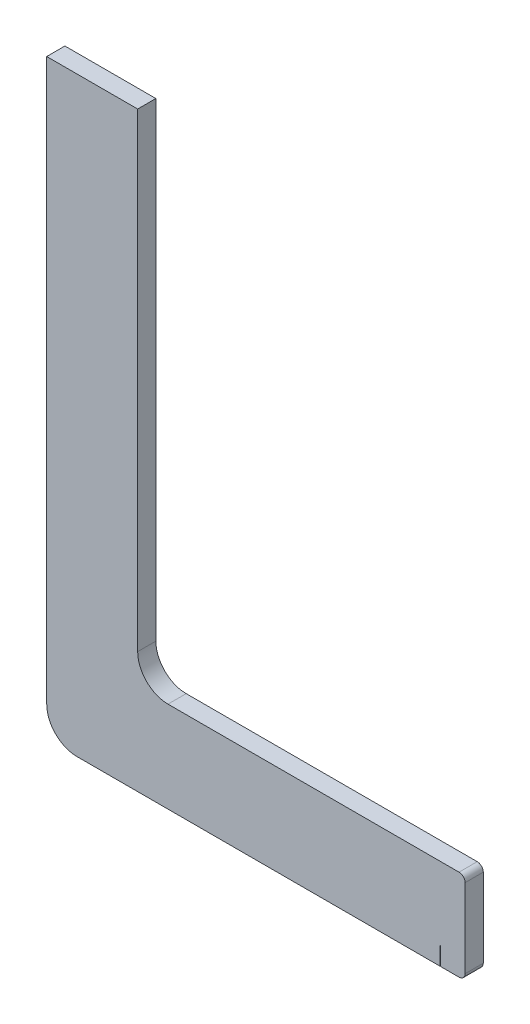
SolidWorks part; units mm, degrees
ref_plane "Front Plane" through (0, 0, 0) normal (0, 0, 1) x (1, 0, 0)
ref_plane "Top Plane" through (0, 0, 0) normal (0, 1, 0) x (1, 0, 0)
ref_plane "Right Plane" through (0, 0, 0) normal (1, 0, 0) x (0, 0, -1)
sketch "Sketch1" plane through (0, 0, 0) normal (0, 0, 1) x (1, 0, 0)
  line L0 (0, -1) -> (0, -92.5)
  line L1 (5, -97.5) -> (68, -97.5)
  line L2 (69, -96.5) -> (69, -83.5)
  line L3 (68, -82.5) -> (20, -82.5)
  line L4 (15, -77.5) -> (15, -1)
  line L5 (14, 0) -> (1, 0)
  line L6 (15, -1) -> (15, 0)
  line L7 (15, 0) -> (14, 0)
  line L8 (0, -1) -> (0, 0)
  line L9 (0, 0) -> (1, 0)
  arc A2 (69, -96.5) -> (68, -97.5) centre (68, -96.5) cw
  arc A3 (69, -83.5) -> (68, -82.5) centre (68, -83.5) ccw
  arc A4 (5, -97.5) -> (0, -92.5) centre (5, -92.5) cw
  arc A5 (15, -77.5) -> (20, -82.5) centre (20, -77.5) ccw
  point P9 (0, 0)
  point P12 (15, 0)
  point P15 (69, -97.5)
  point P18 (69, -82.5)
  point P21 (0, -97.5)
  point P24 (15, -82.5)
  dimension "D6" = 5
  dimension "D1" = 82.5
  dimension "D2" = 15
  dimension "D3" = 69
  dimension "D4" = 15
extrude "Boss-Extrude1" add sketch "Sketch1" along normal blind 3
sketch "Sketch2" plane through (0, -97.5, 0) normal (0, -1, 0) x (1, 0, 0)
  line L0 (0, 1.5) -> (64.9, 1.5) construction
  line L1 (0, 3) -> (0, 0) construction
  line L2 (5, 3) -> (68, 3) construction
  line L3 (64.85, 0) -> (64.95, 0)
  line L4 (64.85, 0) -> (64.85, 3)
  line L5 (64.85, 3) -> (64.95, 3)
  line L6 (64.95, 0) -> (64.95, 3)
  line L7 (64.85, 0) -> (64.95, 3) construction
  line L8 (64.85, 3) -> (64.95, 0) construction
  dimension "D1" = 64.9
  dimension "D2" = 0.1
extrude "Cut-Extrude2" cut sketch "Sketch2" against normal blind 3
equation "\"A.L\"= 0.07m"
equation "\"A.h\"= 0.007m"
equation "\"A.d\"= 0.003m"
equation "\"A.delta\"= 45.0001"
equation "\"A.w\"= 0.02m"
equation "\"A.v\"= 0.03m"
equation "\"A.s\"= 0.014m"
equation "\"A.t\"= 0.007m"
equation "\"B.L\"= 0.065m"
equation "\"B.h\"= 0.008m"
equation "\"B.s\"= 0.016m"
equation "\"B.t\"= 0.008m"
equation "\"C.h\"= 0.0065m"
equation "\"C.d\"= 0.003m"
equation "\"C.L\"= 0.05m"
equation "\"C.wmax\"= 0.005m"
equation "\"D.L\"= 0.06m"
equation "\"D.h\"= 0.008m"
equation "\"D.s\"= 0.012m"
equation "\"D.t\"= 0.008m"
equation "\"a_h\"= 0.0002m"
equation "\"a_d\"= 0.003m"
equation "\"a_L\"= 0.008m"
equation "\"b_h\"= 0.0004m"
equation "\"b_d\"= 0.003m"
equation "\"b_L\"= 0.007m"
equation "\"c_h\"= 0.0001m"
equation "\"c_d\"= 0.003m"
equation "\"c_L\"= 0.01m"
equation "\"d_h\"= 0.0001m"
equation "\"d_d\"= 0.003m"
equation "\"d_L\"= 0.01m"
equation "\"S.h\"= 0.015m"
equation "\"S.L\"= 0.09075m"
equation "\"D1@Sketch1\"=\"S.L\"-\"C.wmax\"-\"C.h\"/2"
equation "\"D2@Sketch1\"=\"S.h\""
equation "\"D3@Sketch1\"=\"C.L\"+\"S.h\"+0.004"
equation "\"D4@Sketch1\"=\"S.h\""
equation "\"D1@Boss-Extrude1\"=\"A.d\""
equation "\"D1@Sketch2\"=\"C.L\"+\"S.h\"-\"d_h\""
equation "\"D2@Sketch2\"=\"d_h\""
